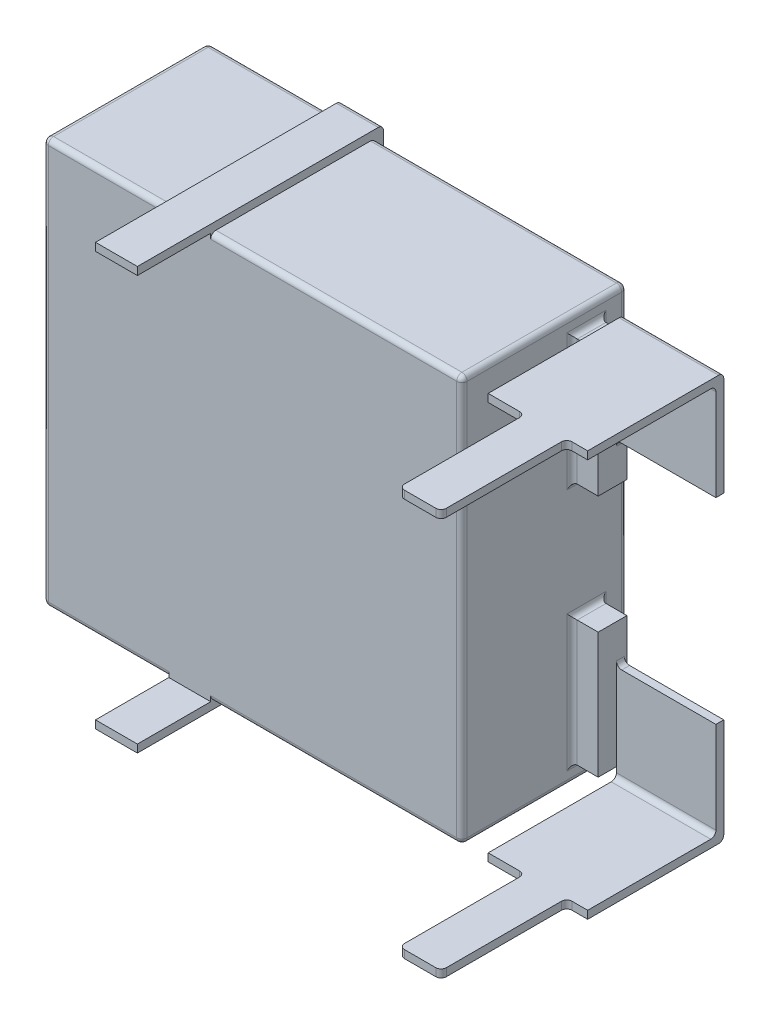
SolidWorks part; units mm, degrees
ref_plane "Front Plane" through (0, 0, 0) normal (0, 0, 1) x (1, 0, 0)
ref_plane "Top Plane" through (0, 0, 0) normal (0, 1, 0) x (1, 0, 0)
ref_plane "Right Plane" through (0, 0, 0) normal (1, 0, 0) x (0, 0, -1)
sketch "Sketch1" plane through (0, 0, 0) normal (0, 0, 1) x (1, 0, 0)
  line L1 (-17.153, 7.8991) -> (-1.153, 7.8991)
  line L2 (-17.153, 7.8991) -> (-17.153, -7.6009)
  line L3 (-17.153, -7.6009) -> (-1.153, -7.6009)
  line L4 (-1.153, 7.8991) -> (-1.153, -7.6009)
  dimension "D1" = 15.5
  dimension "D2" = 16
extrude "Boss-Extrude1" add sketch "Sketch1" along normal mid plane 6.3 contours L2 L1 L4 L3
sketch "Sketch2" plane through (-17.153, 0, 0) normal (-1, 0, 0) x (0, 0, 1)
  line L0 (3.15, 7.8991) -> (-3.15, 7.8991) construction
  line L1 (-2.4198, 0.5991) -> (2.4198, 0.5991)
  line L2 (-2.4198, 0.5991) -> (-2.4198, 7.5991)
  line L3 (-2.4198, 7.5991) -> (2.4198, 7.5991)
  line L4 (2.4198, 0.5991) -> (2.4198, 7.5991)
  line L5 (-2.4198, 0.5991) -> (2.4198, 7.5991) construction
  line L6 (-2.4198, 7.5991) -> (2.4198, 0.5991) construction
  line L7 (3.15, -7.6009) -> (-3.15, -7.6009) construction
  line L8 (2.4198, -7.3009) -> (-2.4198, -7.3009)
  line L9 (2.4198, -7.3009) -> (2.4198, -0.3009)
  line L10 (2.4198, -0.3009) -> (-2.4198, -0.3009)
  line L11 (-2.4198, -7.3009) -> (-2.4198, -0.3009)
  line L12 (2.4198, -7.3009) -> (-2.4198, -0.3009) construction
  line L13 (2.4198, -0.3009) -> (-2.4198, -7.3009) construction
  line L14 (-2.4198, -7.6009) -> (-2.4198, -7.3009) construction
  line L15 (-2.4198, 7.8991) -> (-2.4198, 7.5991) construction
  line L16 (-2.4198, 7.5991) -> (-3.15, 7.5991) construction
  line L17 (-3.15, 7.8991) -> (-3.15, -7.6009) construction
  line L18 (-2.4198, -0.3009) -> (-3.15, -0.3009) construction
  line L19 (0, 7.8991) -> (0, -7.6009) construction
  point P0 (0, 4.0991)
  point P7 (0, -3.8009)
  point P22 (0, 0)
  point P23 (0, 0)
  point P24 (0, 0)
  point P25 (0, 0)
  point P26 (0, 0)
  dimension "D1" = 7
  dimension "D2" = 7.9
extrude "Cut-Extrude1" cut sketch "Sketch2" against normal blind 10
sketch "Sketch4" plane through (-1.153, 0, 0) normal (1, 0, 0) x (0, 0, -1)
  line L0 (2.15, 7.1991) -> (3.15, 7.1991) construction
  line L1 (2.15, 7.1991) -> (1.0536, 7.1991)
  line L2 (2.15, 7.1991) -> (2.15, 2.3991)
  line L3 (2.15, 2.3991) -> (1.0536, 2.3991)
  line L4 (1.0536, 7.1991) -> (1.0536, 2.3991)
  line L5 (2.15, -2.1009) -> (1.0536, -2.1009)
  line L6 (2.15, -2.1009) -> (2.15, -6.9009)
  line L7 (2.15, -6.9009) -> (1.0536, -6.9009)
  line L8 (1.0536, -2.1009) -> (1.0536, -6.9009)
  line L9 (3.15, 7.8991) -> (3.15, -7.6009) construction
  line L10 (3.15, 7.1991) -> (2.15, 7.1991) construction
  line L11 (2.15, 7.8991) -> (2.15, 7.1991) construction
  line L12 (-3.15, 7.8991) -> (3.15, 7.8991) construction
  line L13 (2.15, -6.9009) -> (3.15, -6.9009) construction
  line L14 (3.15, -6.9009) -> (2.15, -6.9009) construction
  line L15 (2.15, -6.9009) -> (2.15, -7.6009) construction
  line L16 (-3.15, -7.6009) -> (3.15, -7.6009) construction
  point P12 (1.6018, 7.1991)
  dimension "D1" = 14.1
  dimension "D2" = 4.5
  dimension "D3" = 1
extrude "Boss-Extrude3" add sketch "Sketch4" along normal blind 1 contours L6 L5 L8 L7 | L2 L1 L4 L3
fillet "Fillet2" radius 0.2 8 edges at (-1.153, 4.7991, -2.15) (-1.153, -4.5009, -1.0536) (-1.153, 4.7991, -1.0536) (-1.153, -4.5009, -2.15) (-1.153, 7.1991, -1.6018) (-1.153, -2.1009, -1.6018) (-1.153, -6.9009, -1.6018) (-1.153, 2.3991, -1.6018)
sketch "Sketch5" plane through (-0.153, 0, 0) normal (1, 0, 0) x (0, 0, -1)
  line L0 (-3.15, 7.8991) -> (3.15, 7.8991) construction
  line L1 (2.0514, 3.8991) -> (1.7514, 3.8991)
  line L2 (2.0514, 3.8991) -> (2.0514, 7.8991)
  line L3 (2.0514, 7.8991) -> (1.7514, 7.8991)
  line L4 (1.7514, 3.8991) -> (1.7514, 7.8991)
  line L5 (-3.15, 0.1491) -> (3.15, 0.1491)
  line L6 (-3.15, 7.8991) -> (-3.15, -7.6009) construction
  line L11 (3.15, 7.8991) -> (3.15, -7.6009) construction
  line L12 (2.0514, -7.6009) -> (1.7514, -7.6009)
  line L13 (1.7514, -3.6009) -> (1.7514, -7.6009)
  line L14 (2.0514, -3.6009) -> (1.7514, -3.6009)
  line L15 (2.0514, -3.6009) -> (2.0514, -7.6009)
  line M3 (2.15, 7.1991) -> (1.0536, 7.1991)
  dimension "D1" = 0.3
  dimension "D2" = 4
extrude "Boss-Extrude4" add sketch "Sketch5" along normal blind 3.8 contours L15 L14 L13 L12 | L4 L1 L2 M3 | L2 L1 L4 L3 region at (-0.153, 5.5491, -1.9014) region at (-0.153, -5.6009, -1.9014)
sketch "Sketch6" plane through (0, 0, -1.7514) normal (0, 0, 1) x (1, 0, 0)
  line L0 (-0.153, 7.1991) -> (-0.153, 7.8991) construction
  line L1 (3.647, 7.8991) -> (-0.153, 7.8991)
  line L2 (3.647, 7.8991) -> (3.647, 7.5991)
  line L3 (3.647, 7.5991) -> (-0.153, 7.5991)
  line L4 (-0.153, 7.8991) -> (-0.153, 7.5991)
  line L6 (3.647, 7.8991) -> (3.647, -7.6009) construction
  line L7 (3.647, 0.1491) -> (-1.5986, 0.1491) construction
  line L8 (3.647, -7.3009) -> (-0.153, -7.3009)
  line L9 (-0.153, -7.6009) -> (-0.153, -7.3009)
  line L10 (3.647, -7.6009) -> (-0.153, -7.6009)
  line L11 (3.647, -7.6009) -> (3.647, -7.3009)
  dimension "D1" = 0.3
extrude "Boss-Extrude5" add sketch "Sketch6" along normal blind 4.9 contours L10 L11 L8 L9 | L2 L1 L4 L3 region at (1.747, -7.4509, -1.7514)
sketch "Sketch7" plane through (0, 0, 3.1486) normal (0, 0, 1) x (1, 0, 0)
  line L0 (3.647, 7.8991) -> (-0.153, 7.8991) construction
  line L1 (1.247, 7.8991) -> (2.847, 7.8991)
  line L2 (1.247, 7.8991) -> (1.247, 7.5991)
  line L3 (1.247, 7.5991) -> (2.847, 7.5991)
  line L4 (2.847, 7.8991) -> (2.847, 7.5991)
  line L5 (3.647, 7.5991) -> (-0.153, 7.5991) construction
  line L6 (3.647, 7.8991) -> (3.647, 7.5991) construction
  line L7 (-1.153, 7.8991) -> (-1.153, -7.6009) construction
  line L8 (-1.153, -7.6009) -> (-1.153, 0.1491) construction
  line L9 (-1.153, 0.1491) -> (3.9799, 0.1491) construction
  line L10 (1.247, -7.3009) -> (2.847, -7.3009)
  line L11 (2.847, -7.6009) -> (2.847, -7.3009)
  line L12 (1.247, -7.6009) -> (2.847, -7.6009)
  line L13 (1.247, -7.6009) -> (1.247, -7.3009)
  point P20 (0, 0)
  dimension "D1" = 1.6
  dimension "D2" = 0.8
extrude "Boss-Extrude6" add sketch "Sketch7" along normal blind 4.8
fillet "Fillet3" radius 0.2 14 edges at (1.747, -7.6009, -2.0514) (1.747, -7.3009, -1.7514) (1.747, 7.8991, -2.0514) (1.747, 7.5991, -1.7514) (-0.153, 3.8991, -1.9014) (-0.153, -3.6009, -1.9014) (2.847, 7.7491, 3.1486) (1.247, 7.7491, 3.1486) (1.247, 7.7491, 7.9486) (2.847, 7.7491, 7.9486) (2.847, -7.4509, 7.9486) (1.247, -7.4509, 7.9486) (1.247, -7.4509, 3.1486) (2.847, -7.4509, 3.1486)
sketch "Sketch8" plane through (0, 0, -3.15) normal (0, 0, -1) x (-1, 0, 0)
  line L0 (17.153, 7.8991) -> (17.153, -7.6009) construction
  line L1 (12.353, -7.9009) -> (10.753, -7.9009)
  line L2 (12.353, -7.9009) -> (12.353, 8.1991)
  line L3 (12.353, 8.1991) -> (10.753, 8.1991)
  line L4 (10.753, -7.9009) -> (10.753, 8.1991)
  line L5 (17.153, -7.6009) -> (1.153, -7.6009) construction
  line L6 (17.153, 7.8991) -> (1.153, 7.8991) construction
  dimension "D1" = 1.6
  dimension "D2" = 4.8
  dimension "D3" = 0.3
  dimension "D4" = 0.3
extrude "Boss-Extrude7" add sketch "Sketch8" along normal blind 0.3
sketch "Sketch9" plane through (0, 0, -3.15) normal (0, 0, 1) x (1, 0, 0)
  line L0 (-17.153, 7.8991) -> (-1.153, 7.8991) construction
  line L1 (-12.353, 8.1991) -> (-10.753, 8.1991)
  line L2 (-12.353, 8.1991) -> (-12.353, 7.8991)
  line L3 (-12.353, 7.8991) -> (-10.753, 7.8991)
  line L4 (-10.753, 8.1991) -> (-10.753, 7.8991)
  line L5 (-12.353, 7.8991) -> (-10.753, 7.8991) construction
  line L6 (-12.353, 8.1991) -> (-12.353, -7.9009) construction
  line L7 (-12.353, -7.9009) -> (-12.353, 0.1491) construction
  line L8 (-12.353, 0.1491) -> (-7.1369, 0.1491) construction
  line L9 (-12.353, -7.6009) -> (-10.753, -7.6009)
  line L10 (-10.753, -7.9009) -> (-10.753, -7.6009)
  line L11 (-12.353, -7.9009) -> (-10.753, -7.9009)
  line L12 (-12.353, -7.9009) -> (-12.353, -7.6009)
extrude "Boss-Extrude8" add sketch "Sketch9" along normal blind 9.1 contours L12 L11 L10 L9 | L2 L1 L4 L3 region at (-11.553, -7.7509, -3.15)
fillet "Fillet5" radius 0.2 26 edges at (-5.953, 7.8991, -3.15) (-14.753, 7.8991, -3.15) (-11.553, 8.1991, -3.45) (-17.153, 0.1491, -3.15) (-5.953, -7.6009, -3.15) (-14.753, -7.6009, -3.15) (-11.553, -7.9009, -3.45) (-1.153, -7.6009, 0) (-1.153, 0.1491, 3.15) (-1.153, 0.1491, -3.15) (-1.153, 7.8991, 0) (-5.953, 7.8991, 3.15) (-14.753, 7.8991, 3.15) (-17.153, 0.1491, 3.15) (-5.953, -7.6009, 3.15) (-14.753, -7.6009, 3.15) (-17.153, 7.8991, 0) (-17.153, 4.0991, 2.4198) (-17.153, 7.5991, 0) (-17.153, 4.0991, -2.4198) (-17.153, 0.5991, 0) (-17.153, -3.8009, 2.4198) (-17.153, -0.3009, 0) (-17.153, -3.8009, -2.4198) (-17.153, -7.3009, 0) (-17.153, -7.6009, 0)
